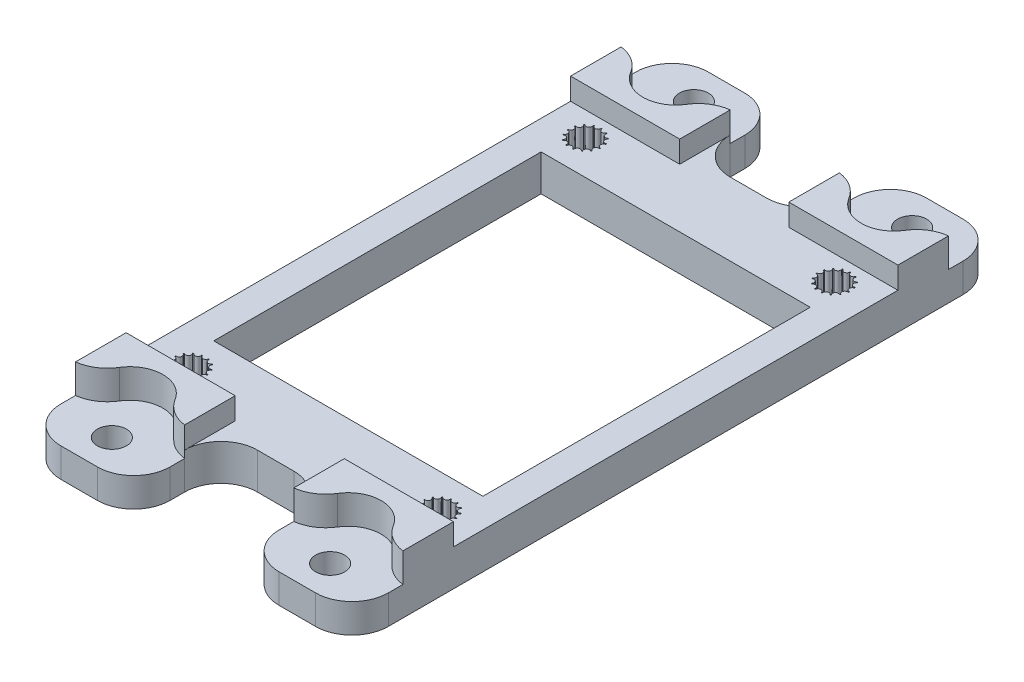
SolidWorks part; units mm, degrees
ref_plane "Front Plane" through (0, 0, 0) normal (0, 0, 1) x (1, 0, 0)
ref_plane "Top Plane" through (0, 0, 0) normal (0, 1, 0) x (1, 0, 0)
ref_plane "Right Plane" through (0, 0, 0) normal (1, 0, 0) x (0, 0, -1)
sketch "Sketch1" plane through (0, 0, 0) normal (0, 1, 0) x (1, 0, 0)
  line L1 (0, 0) -> (45, 0)
  line L2 (0, 0) -> (0, 65)
  line L3 (0, 65) -> (45, 65)
  line L4 (45, 0) -> (45, 65)
  dimension "D1" = 45
  dimension "D2" = 65
extrude "Boss-Extrude1" add sketch "Sketch1" along normal blind 8
sketch "Sketch2" plane through (0, 8, 0) normal (0, 1, 0) x (1, 0, 0)
  line L4 (0, 65) -> (0, 0)
  line L5 (0, 0) -> (45, 0)
  line L6 (45, 0) -> (45, 65)
  line L7 (45, 65) -> (0, 65)
  line L8 (0, 65) -> (0, 0)
  line L9 (0, 0) -> (45, 0)
  line L10 (45, 0) -> (45, 65)
  line L11 (45, 65) -> (0, 65)
  circle A0 centre (5.4, 5.3) radius 2.25
  circle A1 centre (5.4, 7.55) radius 0.4
  circle A2 centre (6.3152, 7.3555) radius 0.4
  circle A3 centre (7.0721, 6.8055) radius 0.4
  circle A4 centre (7.5399, 5.9953) radius 0.4
  circle A5 centre (7.6377, 5.0648) radius 0.4
  circle A6 centre (7.3486, 4.175) radius 0.4
  circle A7 centre (6.7225, 3.4797) radius 0.4
  circle A8 centre (5.8678, 3.0992) radius 0.4
  circle A9 centre (4.9322, 3.0992) radius 0.4
  circle A10 centre (4.0775, 3.4797) radius 0.4
  circle A11 centre (3.4514, 4.175) radius 0.4
  circle A12 centre (3.1623, 5.0648) radius 0.4
  circle A13 centre (3.2601, 5.9953) radius 0.4
  circle A14 centre (3.7279, 6.8055) radius 0.4
  circle A15 centre (4.4848, 7.3555) radius 0.4
  point P9 (0, 0)
  point P38 (5.4, 5.3)
  dimension "D4" = 4.5
  dimension "D5" = 0.8
  dimension "D2" = 5.3
  dimension "D3" = 5.4
  dimension "D1" = 0
  dimension "D6" = 15
extrude "Cut-Extrude1" cut sketch "Sketch2" against normal blind 8 contours A15 A0 A14 A13 A12 A11 A10 A9 A8 A7 A6 A5 A4 A3 A2 A1
ref_plane "Plane1" through (22.5, 0, 0) normal (-1, 0, 0) x (0, 0, 1)
ref_plane "Plane2" through (0, 0, -32.5) normal (0, 0, -1) x (-1, 0, 0)
mirror "Mirror1" about plane through (0, 0, -32.5) normal (0, 0, -1) of "Cut-Extrude1" second plane through (22.5, 0, 0) second plane normal (-1, 0, 0)
sketch "Sketch3" plane through (0, 8, 0) normal (0, 1, 0) x (1, 0, 0)
  line L1 (0, 0) -> (15, 0)
  line L2 (0, 0) -> (0, -12)
  line L3 (0, -12) -> (15, -12)
  line L4 (15, 0) -> (15, -12)
  circle A0 centre (7.5, -7.5) radius 2
  dimension "D3" = 4
  dimension "D1" = 12
  dimension "D2" = 15
  dimension "D4" = 7.5
  dimension "D5" = 7.5
extrude "Boss-Extrude2" add sketch "Sketch3" against normal blind 8
mirror "Mirror2" about plane through (0, 0, -32.5) normal (0, 0, -1) of "Boss-Extrude2" second plane through (22.5, 0, 0) second plane normal (-1, 0, 0)
fillet "Fillet1" radius 5 12 edges at (0, 4, 12) (15, 4, 0) (15, 4, 12) (45, 4, 12) (30, 4, 12) (30, 4, 0) (0, 4, -77) (15, 4, -77) (15, 4, -65) (45, 4, -77) (30, 4, -65) (30, 4, -77)
sketch "Sketch4" plane through (0, 8, 0) normal (0, 1, 0) x (1, 0, 0)
  line L0 (3, -5) -> (0, -5)
  line L1 (0, -5) -> (3, -5)
  line L2 (12, -5) -> (15, -5)
  line L3 (15, -5) -> (15, -14.0562)
  line L4 (15, -14.0562) -> (0, -14.0562)
  line L5 (0, -14.0562) -> (0, -5)
  arc A0 (12, -5) -> (3, -5) centre (7.5, -5) ccw
  dimension "D1" = 9
extrude "Cut-Extrude2" cut sketch "Sketch4" against normal blind 4 contours L2 A0 L0 L5 L4 L3
mirror "Mirror4" about plane through (0, 0, -32.5) normal (0, 0, -1) of "Cut-Extrude2" second plane through (22.5, 0, 0) second plane normal (-1, 0, 0)
fillet "Fillet2" radius 5 24 edges at (13.5, 4, 5) (1.5, 8, 5) (13.5, 8, 5) (12, 6, 5) (1.5, 4, 5) (3, 6, 5) (31.5, 4, 5) (33, 6, 5) (43.5, 8, 5) (42, 6, 5) (43.5, 4, 5) (31.5, 8, 5) (13.5, 4, -70) (12, 6, -70) (1.5, 8, -70) (3, 6, -70) (1.5, 4, -70) (13.5, 8, -70) (31.5, 4, -70) (43.5, 8, -70) (31.5, 8, -70) (33, 6, -70) (43.5, 4, -70) (42, 6, -70)
sketch "Sketch5" plane through (0, 8, 0) normal (0, 1, 0) x (1, 0, 0)
  line L0 (2.75, 32.5) -> (-2.75, 32.5) construction
  line L1 (4, 55) -> (41, 55)
  line L2 (4, 55) -> (4, 10)
  line L3 (4, 10) -> (41, 10)
  line L4 (41, 55) -> (41, 10)
  line L5 (4, 55) -> (41, 10) construction
  line L6 (4, 10) -> (41, 55) construction
  line L7 (22.5, 4.4) -> (22.5, -4.4) construction
  line L8 (45, -5) -> (45, 70) construction
  line L9 (25, 65) -> (20, 65) construction
  point P0 (22.5, 32.5)
  dimension "D1" = 4
  dimension "D2" = 10
extrude "Cut-Extrude3" cut sketch "Sketch5" against normal blind 13
sketch "Sketch6" plane through (0, 8, 0) normal (0, 1, 0) x (1, 0, 0)
  line L0 (22.5, 35.4068) -> (22.5, 29.0608) construction
  line L1 (22.5, 4.4) -> (22.5, -4.4) construction
  line L2 (22.5, 29.0608) -> (22.5, 32.5) construction
  line L3 (2.75, 32.5) -> (-2.75, 32.5) construction
  line L4 (22.5, 32.5) -> (23.179, 32.5) construction
  line L6 (-12.0621, 63.05) -> (57.0621, 63.05)
  line L7 (-12.0621, 63.05) -> (-12.0621, 1.95)
  line L8 (-12.0621, 1.95) -> (57.0621, 1.95)
  line L9 (57.0621, 63.05) -> (57.0621, 1.95)
  line L10 (-12.0621, 63.05) -> (57.0621, 1.95) construction
  line L11 (-12.0621, 1.95) -> (57.0621, 63.05) construction
  line L12 (15, -7) -> (30, -7)
  line L13 (15, -7) -> (15, 72)
  line L14 (15, 72) -> (30, 72)
  line L15 (30, -7) -> (30, 72)
  line L16 (15, -7) -> (30, 72) construction
  line L17 (15, 72) -> (30, -7) construction
  arc A0 (35, 77) -> (30, 72) centre (35, 72) ccw construction
  dimension "D1" = 61.1
extrude "Cut-Extrude4" cut sketch "Sketch6" against normal blind 3 contours L6 L15 L14 L13 | L8 L15 L6 L13 | L8 L13 L6 L7 | L15 L8 L9 L6 | L12 L15 L8 L13
